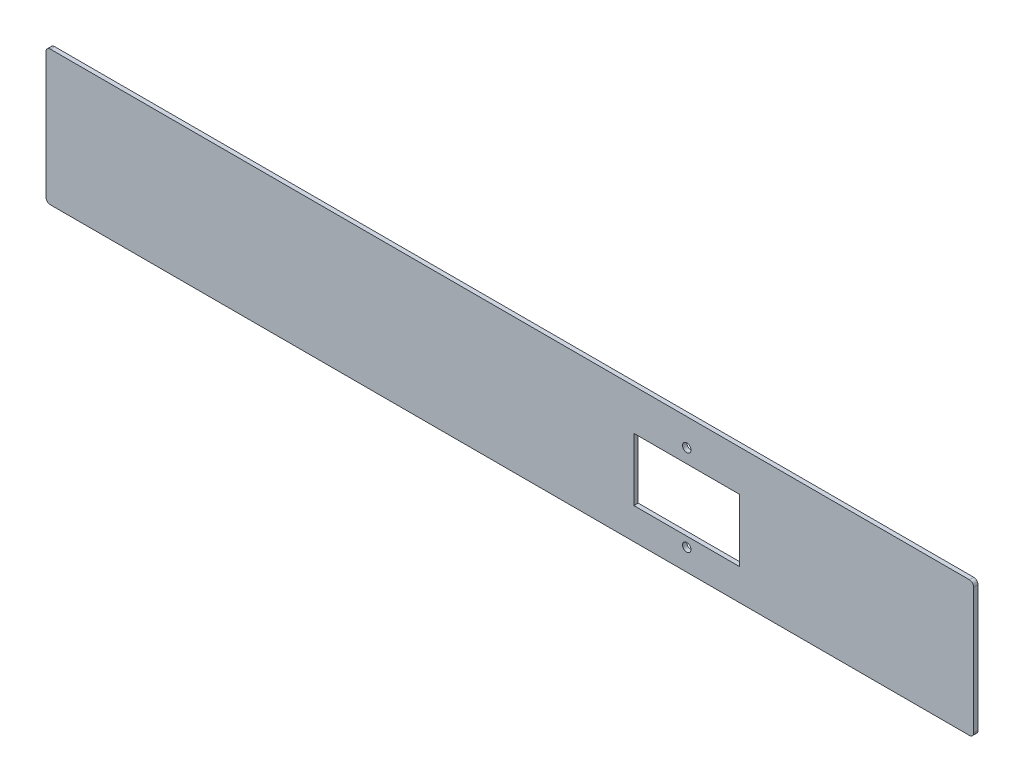
SolidWorks part; units mm, degrees
ref_plane "Front Plane" through (0, 0, 0) normal (0, 0, 1) x (1, 0, 0)
ref_plane "Top Plane" through (0, 0, 0) normal (0, 1, 0) x (1, 0, 0)
ref_plane "Right Plane" through (0, 0, 0) normal (1, 0, 0) x (0, 0, -1)
sketch "Sketch1" plane through (0, 0, 0) normal (0, 0, 1) x (1, 0, 0)
  line L1 (-351.9248, 30.2035) -> (78.0752, 30.2035)
  line L2 (-351.9248, 30.2035) -> (-351.9248, -32.2965)
  line L3 (-351.9248, -32.2965) -> (78.0752, -32.2965)
  line L4 (78.0752, 30.2035) -> (78.0752, -32.2965)
  line L5 (-79.4248, 11.2035) -> (-30.4248, 11.2035)
  line L6 (-79.4248, 11.2035) -> (-79.4248, -17.7965)
  line L7 (-79.4248, -17.7965) -> (-30.4248, -17.7965)
  line L8 (-30.4248, 11.2035) -> (-30.4248, -17.7965)
  circle A0 centre (-54.9248, 17.7035) radius 1.95
  circle A1 centre (-54.9248, -22.2965) radius 1.95
  point P12 (-54.9248, 11.2035)
  dimension "D3" = 133
  dimension "D4" = 40
  dimension "D1" = 430
  dimension "D2" = 62.5
  dimension "D5" = 10
  dimension "D6" = 49
  dimension "D7" = 29
  dimension "D8" = 6.5
extrude "Boss-Extrude1" add sketch "Sketch1" along normal blind 2
fillet "Fillet1" radius 2 4 edges at (78.0752, 30.2035, 1) (78.0752, -32.2965, 1) (-351.9248, -32.2965, 1) (-351.9248, 30.2035, 1)
